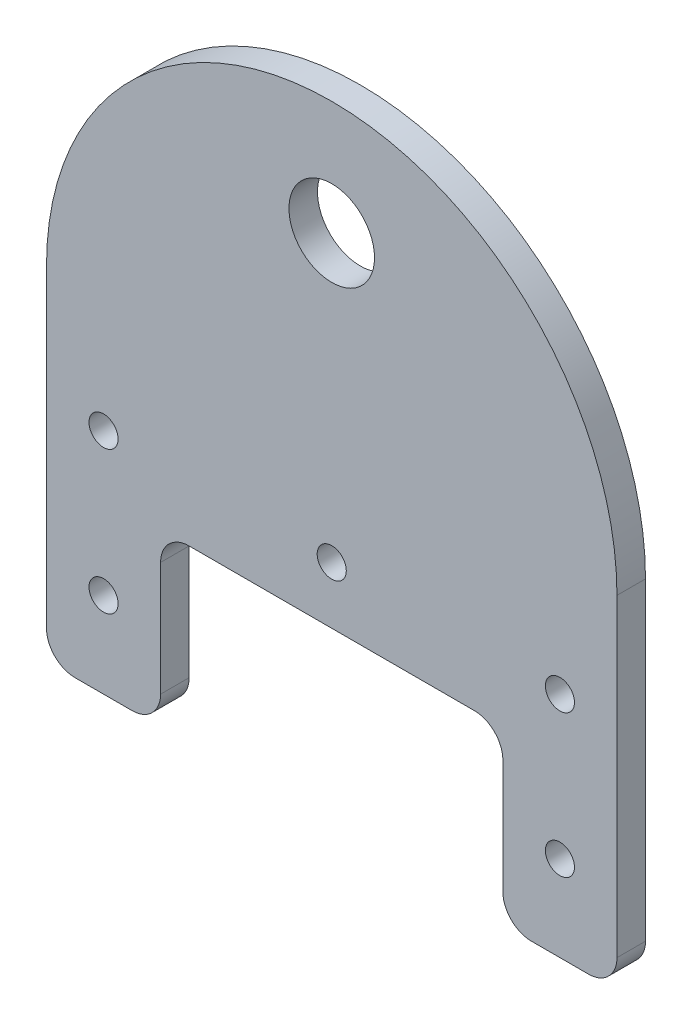
SolidWorks part; units mm, degrees
ref_plane "正面" through (0, 0, 0) normal (0, 0, 1) x (1, 0, 0)
ref_plane "平面" through (0, 0, 0) normal (0, 1, 0) x (1, 0, 0)
ref_plane "右側面" through (0, 0, 0) normal (1, 0, 0) x (0, 0, -1)
sketch "ｽｹｯﾁ1" plane through (0, 0, 0) normal (0, 0, 1) x (1, 0, 0)
  line L0 (-50, -60) -> (50, -60)
  line L1 (-50, -30) -> (-50, -60)
  line L2 (50, -30) -> (50, -60)
  line L3 (0, 0) -> (0, -30) construction
  line L4 (-40, -30) -> (-40, -50) construction
  line L5 (-40, -50) -> (40, -50) construction
  line L6 (40, -50) -> (40, -30) construction
  line L7 (-50, -30) -> (50, -30) construction
  circle A0 centre (0, 0) radius 7.5
  arc A2 (-50, -30) -> (50, -30) centre (0, -30) cw
  circle A3 centre (-40, -50) radius 2.55
  circle A4 centre (0, -50) radius 2.55
  circle A5 centre (40, -50) radius 2.55
  dimension "D1" = 100
  dimension "D2" = 15
  dimension "D3" = 30
  dimension "D4" = 30
  dimension "D8" = 5.1
  dimension "D5" = 10
  dimension "D6" = 10
  dimension "D7" = 10
extrude "ﾎﾞｽ - 押し出し1" add sketch "ｽｹｯﾁ1" along normal blind 5
sketch "ｽｹｯﾁ2" plane through (0, 0, 5) normal (0, 0, 1) x (1, 0, 0)
  line L0 (0, 0) -> (0, -89.872) construction
  line L1 (-50, -60) -> (-30, -60)
  line L2 (-50, -60) -> (-50, -90)
  line L3 (-50, -90) -> (-30, -90)
  line L4 (-30, -60) -> (-30, -90)
  line L5 (-40, -90) -> (-40, -60) construction
  line L6 (40, -90) -> (40, -60) construction
  line L7 (30, -60) -> (30, -90)
  line L8 (50, -90) -> (30, -90)
  line L9 (50, -60) -> (50, -90)
  line L10 (50, -60) -> (30, -60)
  circle A0 centre (-40, -75) radius 2.55
  circle A1 centre (-40, -50) radius 2.55 construction
  circle A2 centre (40, -75) radius 2.55
  dimension "D1" = 30
  dimension "D2" = 20
extrude "ﾎﾞｽ - 押し出し2" add sketch "ｽｹｯﾁ2" against normal up to surface (5 mm away) up to face at (-37.45, -50, 0)
fillet "ﾌｨﾚｯﾄ1" radius 5 6 edges at (-30, -60, 2.5) (30, -60, 2.5) (50, -90, 2.5) (30, -90, 2.5) (-30, -90, 2.5) (-50, -90, 2.5)
